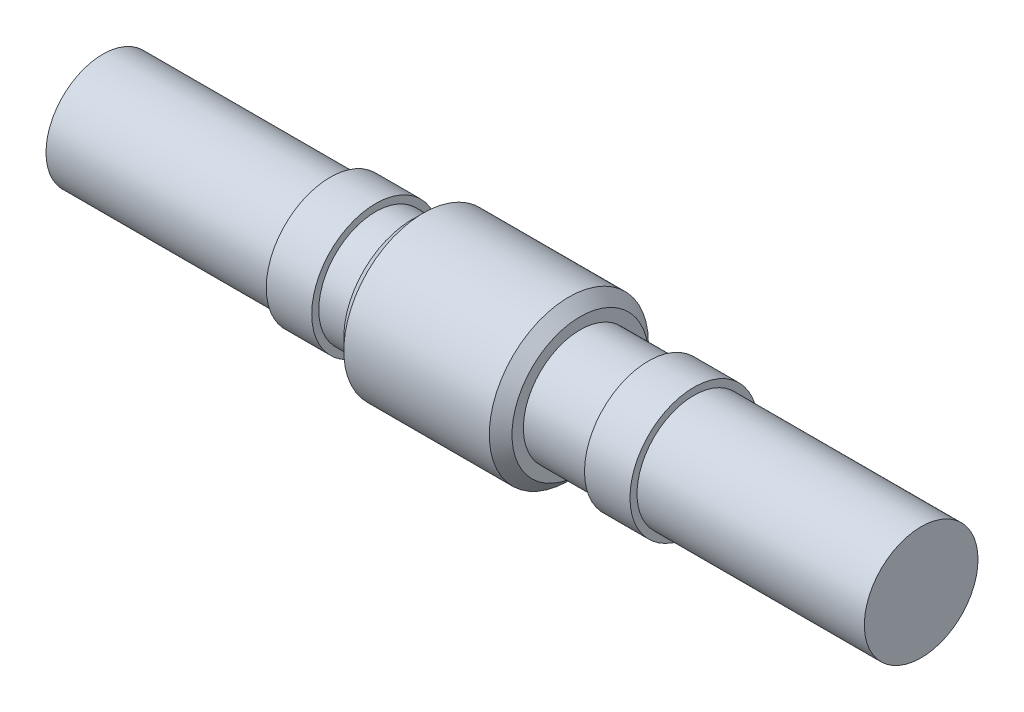
SolidWorks part; units mm, degrees
ref_plane "Frontal" through (0, 0, 0) normal (0, 0, 1) x (1, 0, 0)
ref_plane "Superior" through (0, 0, 0) normal (0, 1, 0) x (1, 0, 0)
ref_plane "Izquierda" through (0, 0, 0) normal (1, 0, 0) x (0, 0, -1)
sketch "Croquis1" plane through (0, 0, 0) normal (1, 0, 0) x (0, 0, -1)
  circle A0 centre (0, 0) radius 35
  dimension "D1" = 70
extrude "Saliente-Extruir1" add sketch "Croquis1" along normal mid plane 74
ref_plane "Plano1" through (7, 0, 0) normal (-1, 0, 0) x (0, 0, 1)
chamfer "Chaflán1" distance 5 angle 45 2 edges at (37, 0, -35) (-37, 0, -35)
sketch "Croquis2" plane through (-37, 0, 0) normal (-1, 0, 0) x (0, 0, 1)
  circle A0 centre (0, 0) radius 25
  dimension "D1" = 50
extrude "Saliente-Extruir2" add sketch "Croquis2" along normal blind 16
sketch "Croquis3" plane through (-53, 0, 0) normal (-1, 0, 0) x (0, 0, 1)
  circle A0 centre (0, 0) radius 28.1
  dimension "D1" = 56.2
extrude "Saliente-Extruir3" add sketch "Croquis3" along normal blind 120
chamfer "Chaflán2" [suppressed] distance 2.5 angle 45
sketch "Croquis4" plane through (37, 0, 0) normal (1, 0, 0) x (0, 0, -1)
  circle A0 centre (0, 0) radius 25
  dimension "D1" = 50
extrude "Saliente-Extruir4" add sketch "Croquis4" along normal blind 30
sketch "Croquis5" plane through (67, 0, 0) normal (1, 0, 0) x (0, 0, -1)
  circle A0 centre (0, 0) radius 28.1
  dimension "D1" = 56.2
extrude "Saliente-Extruir5" add sketch "Croquis5" along normal blind 120
chamfer "Chaflán3" [suppressed] distance 2.5 angle 45
sketch "Croquis6" plane through (-173, 0, 0) normal (-1, 0, 0) x (0, 0, 1)
  circle A0 centre (0, 0) radius 25
  circle A1 centre (0, 0) radius 28.1
extrude "Cortar-Extruir1" cut sketch "Croquis6" against normal blind 100
sketch "Croquis8" plane through (187, 0, 0) normal (1, 0, 0) x (0, 0, -1)
  circle A0 centre (0, 0) radius 25
  circle A1 centre (0, 0) radius 28.1
extrude "Cortar-Extruir2" cut sketch "Croquis8" against normal blind 100
